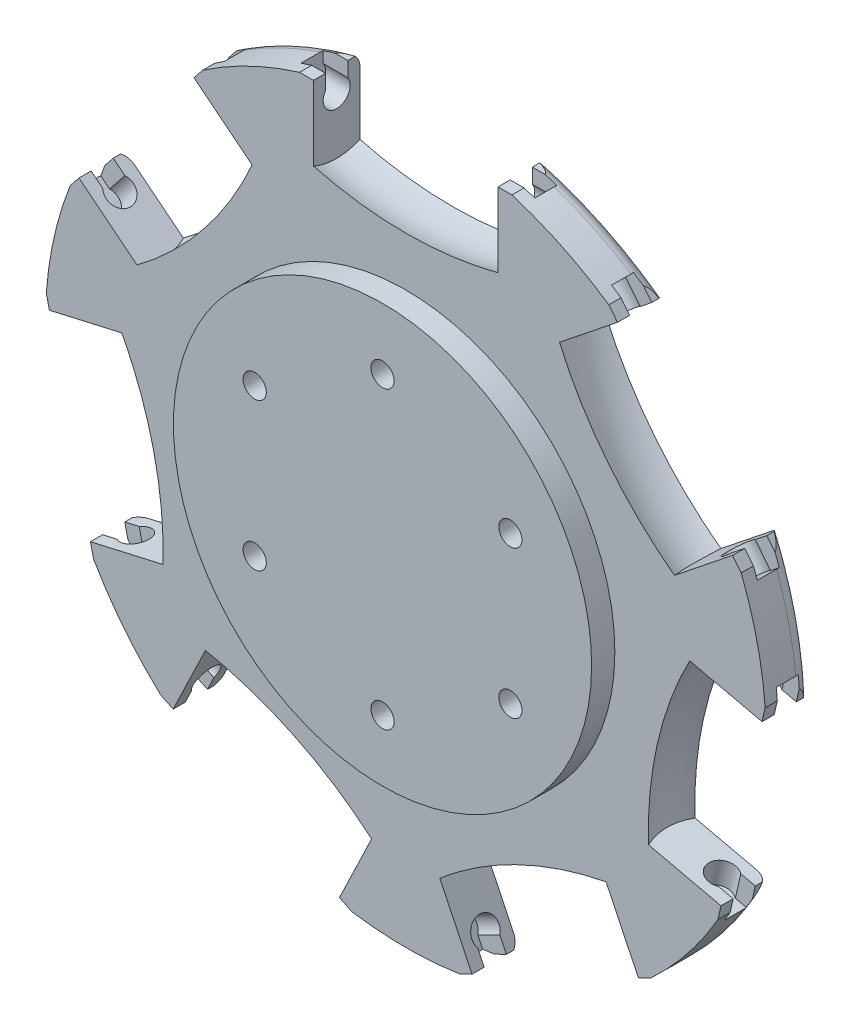
SolidWorks part; units mm, degrees
ref_plane "Front Plane" through (0, 0, 0) normal (0, 0, 1) x (1, 0, 0)
ref_plane "Top Plane" through (0, 0, 0) normal (0, 1, 0) x (1, 0, 0)
ref_plane "Right Plane" through (0, 0, 0) normal (1, 0, 0) x (0, 0, -1)
sketch "Sketch2" plane through (0, 0, 0) normal (0, 0, 1) x (1, 0, 0)
  line L1 (-35.7194, 74.1722) -> (-80.2609, 18.319)
  line L2 (-80.2609, 18.319) -> (-64.3642, -51.3287)
  line L3 (-64.3642, -51.3287) -> (0, -82.3249)
  line L4 (0, -82.3249) -> (64.3642, -51.3287)
  line L5 (64.3642, -51.3287) -> (80.2609, 18.319)
  line L6 (80.2609, 18.319) -> (35.7194, 74.1722)
  line L7 (35.7194, 74.1722) -> (-35.7194, 74.1722)
  circle A0 centre (0, 0) radius 74.1722 construction
  dimension "D1" = 148.3444
extrude "Base heptagonal" add sketch "Sketch2" along normal mid plane 10
sketch "Sketch3" plane through (0, 0, 0) normal (0, 0, 1) x (1, 0, 0)
  line L2 (-19.8704, 81.4803) -> (-19.8704, 69.2949)
  line L3 (19.8704, 81.4803) -> (19.8704, 69.2949)
  line L4 (-19.8704, 69.2949) -> (19.8704, 69.2949) construction
  line L5 (0, 51.0921) -> (0, 0) construction
  line L6 (0, 69.2949) -> (0, 51.0921) construction
  line L7 (-19.8704, 69.2949) -> (19.8704, 69.2949)
  line L8 (-19.8704, 69.2949) -> (0, 0) construction
  line L9 (0, 0) -> (19.8704, 69.2949) construction
  line L10 (-80.2609, 18.319) -> (-64.3642, -51.3287) construction
  circle A0 centre (0, 0) radius 74.1722 construction
  arc A3 (-19.8704, 81.4803) -> (19.8704, 81.4803) centre (0, 0) cw
  point P5 (0, 51.0921)
  dimension "D1" = 69.2949
  dimension "D2" = 32.001
  dimension "D3" = 12.1854
revolve "Corte De Rodillo" cut sketch "Sketch3" angle 360 about L4
sketch "Sketch8" plane through (0, 0, 5) normal (0, 0, 1) x (1, 0, 0)
  circle A0 centre (0, 0) radius 15.894
  dimension "D1" = 31.7881
extrude "Relieve de Centro" add sketch "Sketch8" along normal blind 1.3245
pattern_circular "CirPattern2" count 7 over 360 about axis through (0, 0, 6.3245) along (0, 0, 1) of "Corte De Rodillo"
sketch "Sketch9" plane through (-19.8704, 0, 0) normal (1, 0, 0) x (0, 0, -1)
  line L0 (0, 69.2949) -> (0.9, 69.2949) construction
  line L1 (2.3841, 70.9703) -> (2.3841, 74.1722)
  line L2 (2.3841, 74.1722) -> (-2.3841, 74.1722)
  line L3 (-2.3841, 74.1722) -> (-2.3841, 70.9703)
  line L4 (9.5777, 0) -> (-25.2887, 0) construction
  line L5 (0, -3.0804) -> (0, 92.0042) construction
  line L6 (-5, 74.1722) -> (5, 74.1722) construction
  arc A0 (-2.3841, 70.9703) -> (2.3841, 70.9703) centre (0, 69.2949) ccw
  point P12 (0, 74.1722)
  dimension "D1" = 4.7682
  dimension "D2" = 3.2019
extrude "Cut-Extrude1" cut sketch "Sketch9" along normal blind 45.0331 and the other way blind 5.298
pattern_circular "CirPattern3" count 7 over 360 about axis through (0, 0, 6.3245) along (0, 0, 1) of "Cut-Extrude1"
sketch "Sketch11" plane through (0, 0, -5) normal (0, 0, -1) x (-1, 0, 0)
  circle A0 centre (0, 0) radius 45.0331
  dimension "D1" = 90.0662
extrude "Cut-Extrude3" cut sketch "Sketch11" against normal blind 5
sketch "Sketch12" plane through (0, 0, 0) normal (0, 0, -1) x (-1, 0, 0)
  line L0 (62.7552, 0) -> (-24.9157, 0) construction
  circle A0 centre (0, 0) radius 31.7881 construction
  circle A1 centre (0, 31.7881) radius 2.5
  circle A2 centre (27.5293, 15.894) radius 2.5
  circle A3 centre (27.5293, -15.894) radius 2.5
  circle A4 centre (0, -31.7881) radius 2.5
  circle A5 centre (-27.5293, -15.894) radius 2.5
  circle A6 centre (-27.5293, 15.894) radius 2.5
  point P14 (0, 0)
  dimension "D1" = 6
  dimension "D2" = 63.5762
  dimension "D3" = 5
  dimension "D4" = 15.894
extrude "Cut-Extrude4" cut sketch "Sketch12" against normal through all
sketch "Sketch13" plane through (0, 0, -5) normal (0, 0, -1) x (-1, 0, 0)
  circle A0 centre (0, 0) radius 77.6159
  dimension "D1" = 155.2318
extrude "Cut-Extrude-Thin1" cut sketch "Sketch13" against normal blind 10 thin thin type one direction wall 10
sketch "Sketch15" plane through (0, 0, 5) normal (0, 0, 1) x (1, 0, 0)
  circle A0 centre (0, 0) radius 15.894
  dimension "D1" = 31.7881
extrude "Cut-Extrude6" cut sketch "Sketch15" along normal blind 3.5
fillet "Fillet1" radius 3.1788 7 edges at (-33.6763, 69.9295, -5) (-75.6699, 17.2712, -5) (-60.6825, -48.3927, -5) (0, -77.6159, -5) (60.6825, -48.3927, -5) (75.6699, 17.2712, -5) (33.6763, 69.9295, -5)
sketch "Croquis1" plane through (0, 0, 5) normal (0, 0, 1) x (1, 0, 0)
  circle A0 centre (0, 0) radius 45.0331
  circle A1 centre (-27.5293, -15.894) radius 2.5 construction
  circle A2 centre (0, -31.7881) radius 2.5 construction
  circle A3 centre (27.5293, -15.894) radius 2.5 construction
  circle A4 centre (27.5293, 15.894) radius 2.5 construction
  circle A5 centre (0, 31.7881) radius 2.5 construction
  circle A6 centre (-27.5293, 15.894) radius 2.5 construction
  circle A7 centre (-27.5293, -15.894) radius 2.5
  circle A8 centre (0, -31.7881) radius 2.5
  circle A9 centre (27.5293, -15.894) radius 2.5
  circle A10 centre (27.5293, 15.894) radius 2.5
  circle A11 centre (0, 31.7881) radius 2.5
  circle A12 centre (-27.5293, 15.894) radius 2.5
  dimension "D1" = 90.0662
extrude "Saliente-Extruir1" add sketch "Croquis1" along normal blind 5
